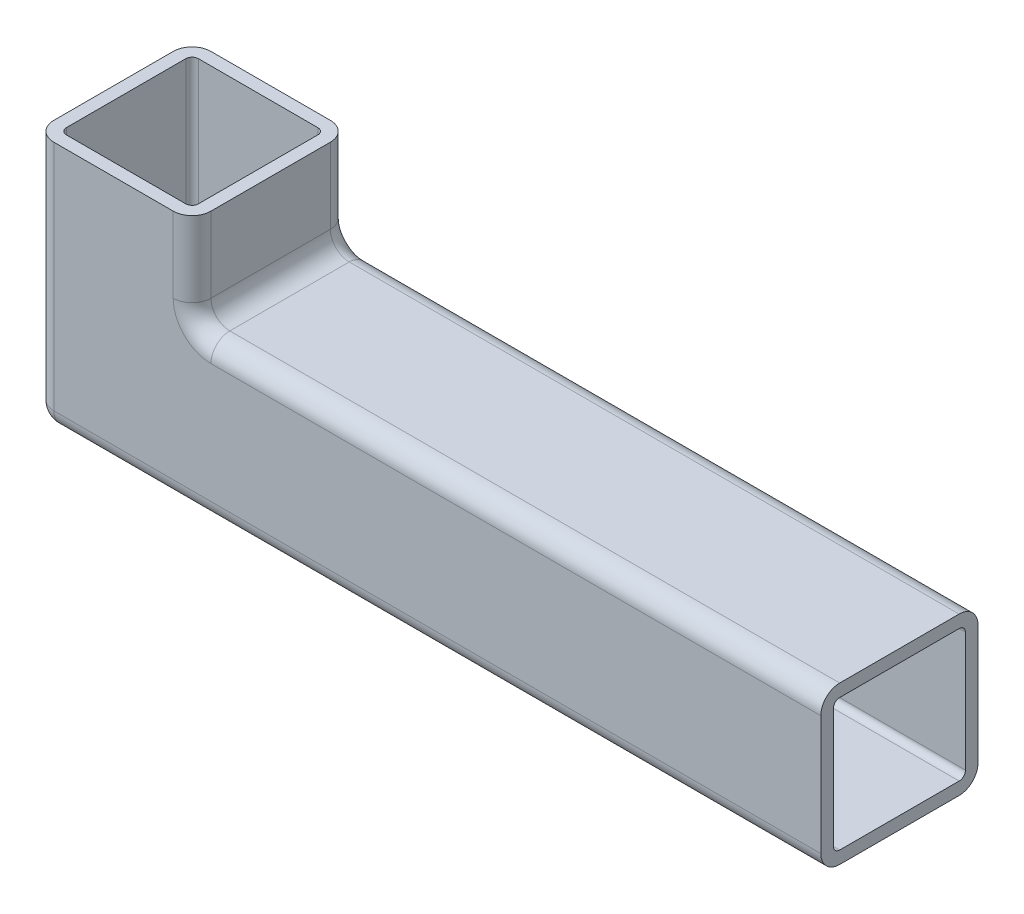
SolidWorks part; units mm, degrees
ref_plane "Front Plane" through (0, 0, 0) normal (0, 0, 1) x (1, 0, 0)
ref_plane "Top Plane" through (0, 0, 0) normal (0, 1, 0) x (1, 0, 0)
ref_plane "Right Plane" through (0, 0, 0) normal (1, 0, 0) x (0, 0, -1)
sketch "Sketch1" plane through (0, 0, 0) normal (0, 0, 1) x (1, 0, 0)
  line L1 (0, 0) -> (125, 0)
  line L2 (0, 0) -> (0, 40)
  line L3 (0, 40) -> (125, 40)
  line L4 (125, 0) -> (125, 40)
  dimension "D1" = 125
  dimension "D2" = 40
extrude "Boss-Extrude1" add sketch "Sketch1" along normal blind 25
sketch "Sketch2" plane through (0, 0, 25) normal (0, 0, 1) x (1, 0, 0)
  line L0 (125, 40) -> (0, 40) construction
  line L1 (25, 40) -> (125, 40)
  line L2 (25, 40) -> (25, 25)
  line L3 (25, 25) -> (125, 25)
  line L4 (125, 40) -> (125, 25)
  line L5 (125, 0) -> (125, 40) construction
  line L6 (0, 40) -> (0, 0) construction
  line L7 (0, 0) -> (125, 0) construction
  dimension "D1" = 25
  dimension "D2" = 25
extrude "Cut-Extrude1" cut sketch "Sketch2" against normal blind 25
sketch "Sketch3" plane through (125, 0, 0) normal (1, 0, 0) x (0, 0, -1)
  line L0 (-25, 0) -> (-25, 25) construction
  line L1 (-23, 23) -> (-2, 23)
  line L2 (-23, 23) -> (-23, 2)
  line L3 (-23, 2) -> (-2, 2)
  line L4 (-2, 23) -> (-2, 2)
  line L5 (0, 0) -> (0, 25) construction
  line L7 (0, 25) -> (-25, 25) construction
  line L8 (-25, 0) -> (0, 0) construction
  dimension "D1" = 2
  dimension "D2" = 2
  dimension "D3" = 2
  dimension "2" = 2
extrude "Cut-Extrude2" cut sketch "Sketch3" against normal blind 123
sketch "Sketch4" plane through (0, 40, 0) normal (0, 1, 0) x (1, 0, 0)
  line L0 (25, 0) -> (0, 0) construction
  line L1 (23, -2) -> (2, -2)
  line L2 (23, -2) -> (23, -23)
  line L3 (23, -23) -> (2, -23)
  line L4 (2, -2) -> (2, -23)
  line L5 (25, 0) -> (25, -25) construction
  line L6 (25, -25) -> (0, -25) construction
  line L7 (0, -25) -> (0, 0) construction
  dimension "D1" = 2
  dimension "D2" = 2
  dimension "D3" = 2
  dimension "D4" = 2
extrude "Cut-Extrude3" cut sketch "Sketch4" against normal blind 38
fillet "Fillet3" radius 1 2 edges at (63.5, 2, 2) (2, 21, 2)
fillet "Fillet4" radius 1 2 edges at (63.5, 2, 23) (2, 21, 23)
fillet "Fillet5" radius 1 1 edges at (74, 23, 2)
fillet "Fillet6" radius 1 1 edges at (74, 23, 23)
fillet "Fillet7" radius 1 1 edges at (23, 31, 23)
fillet "Fillet8" radius 1 1 edges at (23, 31, 2)
fillet "Fillet9" radius 3 5 edges at (62.5, 0, 25) (75, 25, 25) (25, 25, 12.5) (25, 32.5, 25) (0, 20, 25)
fillet "Fillet11" radius 3 5 edges at (0, 20, 0) (62.5, 0, 0) (76.5, 25, 0) (25.8787, 25.8787, 0) (25, 34, 0)
fillet "Fillet12" radius 3 3 edges at (0.8787, 0.8787, 24.1213) (0, 0, 12.5) (0.8787, 0.8787, 0.8787)
